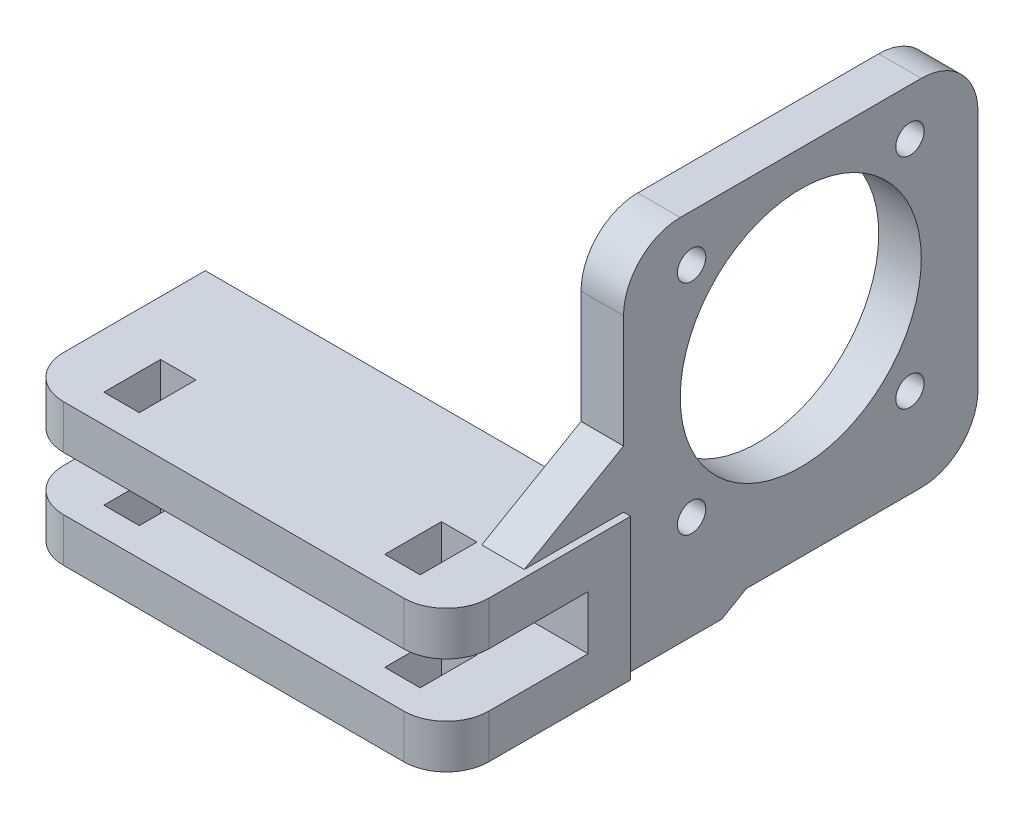
SolidWorks part; units mm, degrees
ref_plane "Plano frontal" through (0, 0, 0) normal (0, 0, 1) x (1, 0, 0)
ref_plane "Plano superior" through (0, 0, 0) normal (0, 1, 0) x (1, 0, 0)
ref_plane "Plano direito" through (0, 0, 0) normal (1, 0, 0) x (0, 0, -1)
sketch "Esboço1" plane through (0, 0, 0) normal (0, 0, 1) x (1, 0, 0)
  line L1 (-15, 5) -> (15, 5)
  line L2 (-15, 5) -> (-15, -5)
  line L3 (-15, -5) -> (15, -5)
  line L4 (15, 5) -> (15, -5)
  line L5 (-15, 5) -> (15, -5) construction
  line L6 (-15, -5) -> (15, 5) construction
  point P0 (0, 0)
  dimension "D1" = 10
  dimension "D2" = 30
extrude "Ressalto-extrusão1" add sketch "Esboço1" along normal blind 13
sketch "Esboço2" plane through (0, 0, 13) normal (0, 0, 1) x (1, 0, 0)
  line L0 (15, -5) -> (15, 5) construction
  line L1 (-15, 1.9) -> (15, 1.9)
  line L2 (-15, 1.9) -> (-15, -1.9)
  line L3 (-15, -1.9) -> (15, -1.9)
  line L4 (15, 1.9) -> (15, -1.9)
  line L5 (-15, 1.9) -> (15, -1.9) construction
  line L6 (-15, -1.9) -> (15, 1.9) construction
  point P0 (0, 0)
  dimension "D1" = 3.8
extrude "Corte-extrusão1" cut sketch "Esboço2" against normal blind 10
fillet "Filete1" radius 3 4 edges at (15, -3.45, 13) (15, 3.45, 13) (-15, 3.45, 13) (-15, -3.45, 13)
sketch "Esboço3" plane through (0, 5, 0) normal (0, 1, 0) x (1, 0, 0)
  line L0 (9.9068, -9) -> (-9.9068, -9) construction
  line L1 (12, -13) -> (-12, -13) construction
  line L2 (11.1568, -11) -> (8.6568, -11)
  line L3 (11.1568, -11) -> (11.1568, -7)
  line L4 (11.1568, -7) -> (8.6568, -7)
  line L5 (8.6568, -11) -> (8.6568, -7)
  line L6 (11.1568, -11) -> (8.6568, -7) construction
  line L7 (11.1568, -7) -> (8.6568, -11) construction
  line L8 (-8.6568, -11) -> (-11.1568, -11)
  line L9 (-8.6568, -11) -> (-8.6568, -7)
  line L10 (-8.6568, -7) -> (-11.1568, -7)
  line L11 (-11.1568, -11) -> (-11.1568, -7)
  line L12 (-8.6568, -11) -> (-11.1568, -7) construction
  line L13 (-8.6568, -7) -> (-11.1568, -11) construction
  point P3 (0, -9)
  point P13 (0, 0)
  dimension "D1" = 2.5
  dimension "D2" = 4
  dimension "D3" = 2
extrude "Corte-extrusão2" cut sketch "Esboço3" against normal through all both and the other way through all
ref_plane "Plano1" through (13, 0, 0) normal (1, 0, 0) x (0, 0, -1)
sketch "Esboço4" plane through (13, 0, 0) normal (1, 0, 0) x (0, 0, -1)
  line L0 (0, 5) -> (0, -5) construction
  line L1 (25, 21) -> (0, 21)
  line L2 (25, 21) -> (25, -4)
  line L3 (25, -4) -> (0, -4)
  line L4 (0, 21) -> (0, -4)
  line L5 (25, 21) -> (0, -4) construction
  line L6 (25, -4) -> (0, 21) construction
  line L7 (-10, -5) -> (0, -5) construction
  point P0 (12.5, 8.5)
  point P5 (10.7115, 9.8136)
  point P6 (12.6405, 12.1463)
  dimension "D1" = 25
  dimension "D2" = 1
extrude "Ressalto-extrusão2" add sketch "Esboço4" against normal mid plane 3
chamfer "Chanfro1" distance 5 angle 60 1 edges at (13, -4, 0) first distance on face at (6.5, 0.25, 0)
chamfer "Chanfro2" distance 7 angle 30 1 edges at (13, 5, 0) first distance on face at (9.9068, 5, 9)
sketch "Esboço5" plane through (11.5, 0, 0) normal (-1, 0, 0) x (0, 0, 1)
  line L0 (-25, 21) -> (0, 21) construction
  line L1 (-4.8, 2.3) -> (-20.2, 2.3) construction
  line L2 (-4.8, 2.3) -> (-4.8, 17.7) construction
  line L3 (-4.8, 17.7) -> (-20.2, 17.7) construction
  line L4 (-20.2, 2.3) -> (-20.2, 17.7) construction
  line L5 (-4.8, 2.3) -> (-20.2, 17.7) construction
  line L6 (-4.8, 17.7) -> (-20.2, 2.3) construction
  circle A0 centre (-12.5, 10) radius 8.5
  circle A1 centre (-20.2, 17.7) radius 1
  circle A2 centre (-4.8, 17.7) radius 1
  circle A3 centre (-4.8, 2.3) radius 1
  circle A4 centre (-20.2, 2.3) radius 1
  point P11 (0, 0)
  point P13 (0, 0)
  point P16 (-12.5, 21)
  point P17 (0, 0)
  dimension "D1" = 17
  dimension "D3" = 2
  dimension "D2" = 15.4
  dimension "D4" = 11
extrude "Corte-extrusão3" cut sketch "Esboço5" against normal blind 3
fillet "Filete2" radius 4 3 edges at (13, -4, -25) (13, 21, -25) (13, 21, 0)
